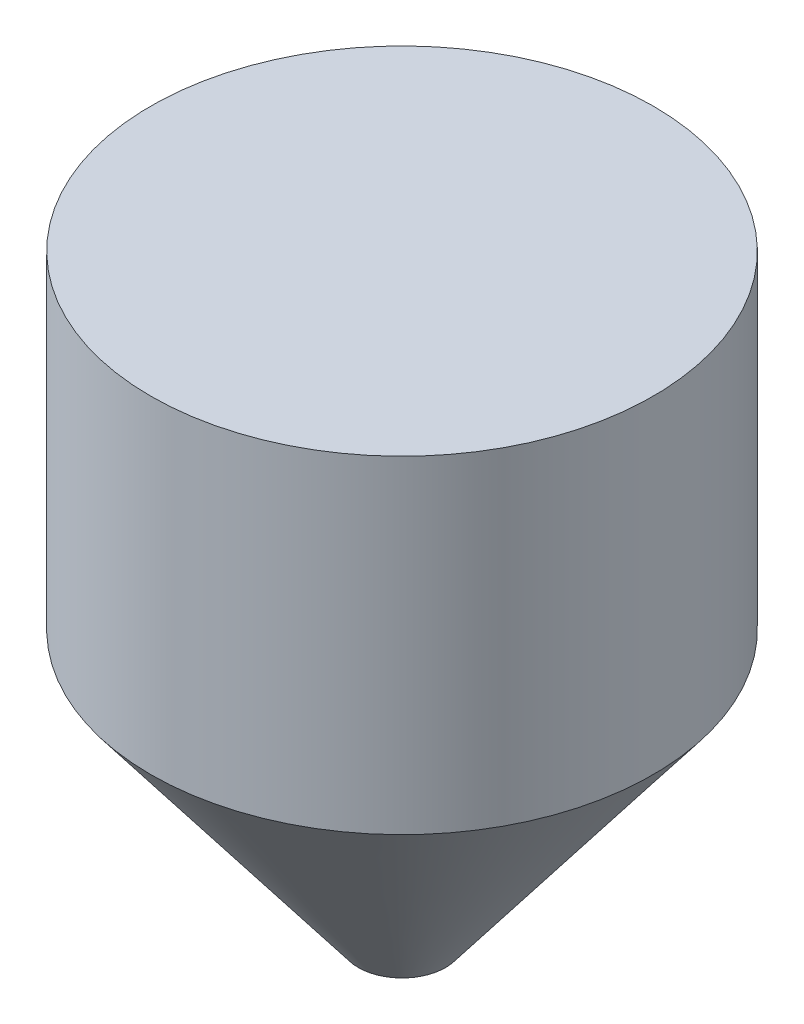
SolidWorks part; units mm, degrees
ref_plane "Alzado" through (0, 0, 0) normal (0, 0, 1) x (1, 0, 0)
ref_plane "Planta" through (0, 0, 0) normal (0, 1, 0) x (1, 0, 0)
ref_plane "Vista lateral" through (0, 0, 0) normal (1, 0, 0) x (0, 0, -1)
sketch "Croquis1" plane through (0, 0, 0) normal (0, 1, 0) x (1, 0, 0)
  circle A0 centre (0, 0) radius 115
  dimension "D1" = 230
ref_plane "Plano1" through (0, -274, 0) normal (0, 1, 0) x (1, 0, 0)
extrude "Saliente-Extruir1" add sketch "Croquis1" against normal blind 150 contours A0
sketch "Croquis2" plane through (0, -150, 0) normal (0, -1, 0) x (1, 0, 0)
  circle A1 centre (0, 0) radius 115
sketch "Croquis3" plane through (0, -274, 0) normal (0, 1, 0) x (1, 0, 0)
  circle A0 centre (0, 0) radius 20
  dimension "D1" = 40
loft "Recubrir1" add profiles "Croquis3", "Croquis2" connector at (-19.9701, -274, 1.0927) connector at (-114.7731, -150, 7.2209)
